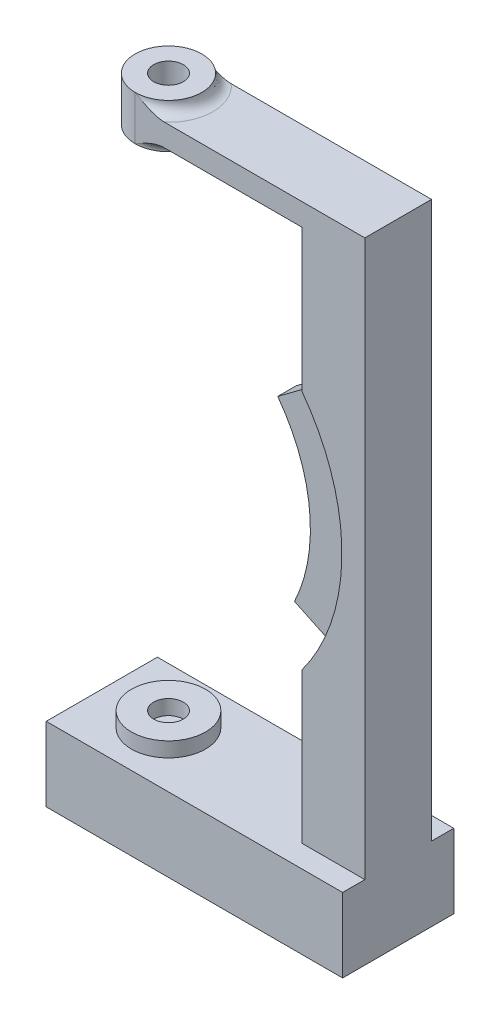
SolidWorks part; units mm, degrees
ref_plane "Front Plane" through (0, 0, 0) normal (0, 0, 1) x (1, 0, 0)
ref_plane "Top Plane" through (0, 0, 0) normal (0, 1, 0) x (1, 0, 0)
ref_plane "Right Plane" through (0, 0, 0) normal (1, 0, 0) x (0, 0, -1)
sketch "Sketch1" plane through (0, 0, 0) normal (0, 1, 0) x (1, 0, 0)
  line L1 (0, 0) -> (-80, 0)
  line L2 (0, 0) -> (0, 30)
  line L3 (0, 30) -> (-80, 30)
  line L4 (-80, 0) -> (-80, 30)
  dimension "D1" = 80
  dimension "D2" = 30
extrude "Boss-Extrude1" add sketch "Sketch1" along normal blind 20
sketch "Sketch2" plane through (0, 20, 0) normal (0, 1, 0) x (1, 0, 0)
  line L0 (0, 15) -> (-80, 15) construction
  line L1 (0, 0) -> (0, 30) construction
  line L2 (-80, 30) -> (-80, 0) construction
  line L4 (0, 24) -> (-17, 24)
  line L5 (0, 24) -> (0, 6)
  line L6 (0, 6) -> (-17, 6)
  line L7 (-17, 24) -> (-17, 6)
  dimension "D1" = 18
  dimension "D2" = 17
extrude "Boss-Extrude2" add sketch "Sketch2" along normal blind 150
sketch "Sketch3" plane through (0, 20, 0) normal (0, 1, 0) x (1, 0, 0)
  line L0 (-80, 15) -> (-45.6224, 15) construction
  line L1 (-80, 30) -> (-80, 0) construction
  circle A0 centre (-62, 15) radius 10
  circle A1 centre (-62, 15) radius 4
  dimension "D2" = 20
  dimension "D3" = 8
  dimension "D1" = 18
extrude "Boss-Extrude3" add sketch "Sketch3" along normal blind 4
sketch "Sketch4" plane through (0, 170, 0) normal (0, 1, 0) x (1, 0, 0)
  line L0 (0, 6) -> (0, 24) construction
  line L1 (0, 24) -> (-62, 24)
  line L2 (0, 24) -> (0, 6)
  line L3 (0, 6) -> (-62, 6)
  line L5 (-17, 6) -> (0, 6) construction
  line L6 (0, 24) -> (-17, 24) construction
  circle A0 centre (-62, 15) radius 9
  line M6 (0, 6) -> (0, 24)
  line M7 (0, 24) -> (-17, 24)
  line M8 (-17, 24) -> (-17, 6)
  line M9 (-17, 6) -> (0, 6)
  dimension "D1" = 62
extrude "Boss-Extrude4" add sketch "Sketch4" against normal blind 6 contours A0 L3 L1 M8 | M9 M6 M7 M8 | A0 region at (-8.5, 170, -15) region at (-36.0189, 170, -15) region at (-62, 170, -15)
extrude "Boss-Extrude5" add sketch "Sketch4<3>" along normal blind 3 contours A0 region at (-62, 170, -15)
sketch "Sketch4<3>" plane through (0, 170, 0) normal (0, 1, 0) x (1, 0, 0) same geometry as "Sketch4"
extrude "Boss-Extrude6" add sketch "Sketch4<4>" against normal blind 3 from offset 6 contours A0 region at (-62, 170, -15) offset against normal yes
sketch "Sketch4<4>" plane through (0, 170, 0) normal (0, 1, 0) x (1, 0, 0) same geometry as "Sketch4"
fillet "Fillet1" radius 3 2 edges at (-53, 164, -15) (-53, 170, -15)
sketch "Sketch5" plane through (0, 173, 0) normal (0, 1, 0) x (1, 0, 0)
  circle A0 centre (-62, 15) radius 4
  dimension "D1" = 8
extrude "Cut-Extrude1" cut sketch "Sketch5" against normal up to next
sketch "Sketch6" plane through (0, 0, -6) normal (0, 0, 1) x (1, 0, 0)
  line L0 (0, 0) -> (0, 93.1) construction
  line L3 (0, 170) -> (0, 20) construction
  line L4 (0, 93.1) -> (-60.7, 93.1) construction
  line L5 (-17, 164) -> (-17, 20) construction
  line L6 (-17, 125.6662) -> (-17, 60.5338)
  arc A0 (-17, 60.5338) -> (-17, 125.6662) centre (-60.7, 93.1) ccw
  dimension "D3" = 109
  dimension "D1" = 93.1
  dimension "D2" = 60.7
extrude "Cut-Extrude3" cut sketch "Sketch6" against normal through all
sketch "Sketch7" plane through (0, 0, -6) normal (0, 0, 1) x (1, 0, 0)
  line L0 (-25.0183, 119.6908) -> (-17, 125.6662)
  line L1 (-20.4918, 74.033) -> (-11.4562, 69.7483)
  arc A0 (-17, 60.5338) -> (-17, 125.6662) centre (-60.7, 93.1) ccw construction
  arc A1 (-11.4562, 69.7483) -> (-17, 125.6662) centre (-60.7, 93.1) ccw
  arc A2 (-20.4918, 74.033) -> (-25.0183, 119.6908) centre (-60.7, 93.1) ccw
  dimension "D1" = 10
extrude "Boss-Extrude7" add sketch "Sketch7" against normal blind 5 from offset 1.5 offset against normal yes
pattern_linear "LPattern1" count 2 spacing 10 along (0, 0, -1) of "Boss-Extrude7"
